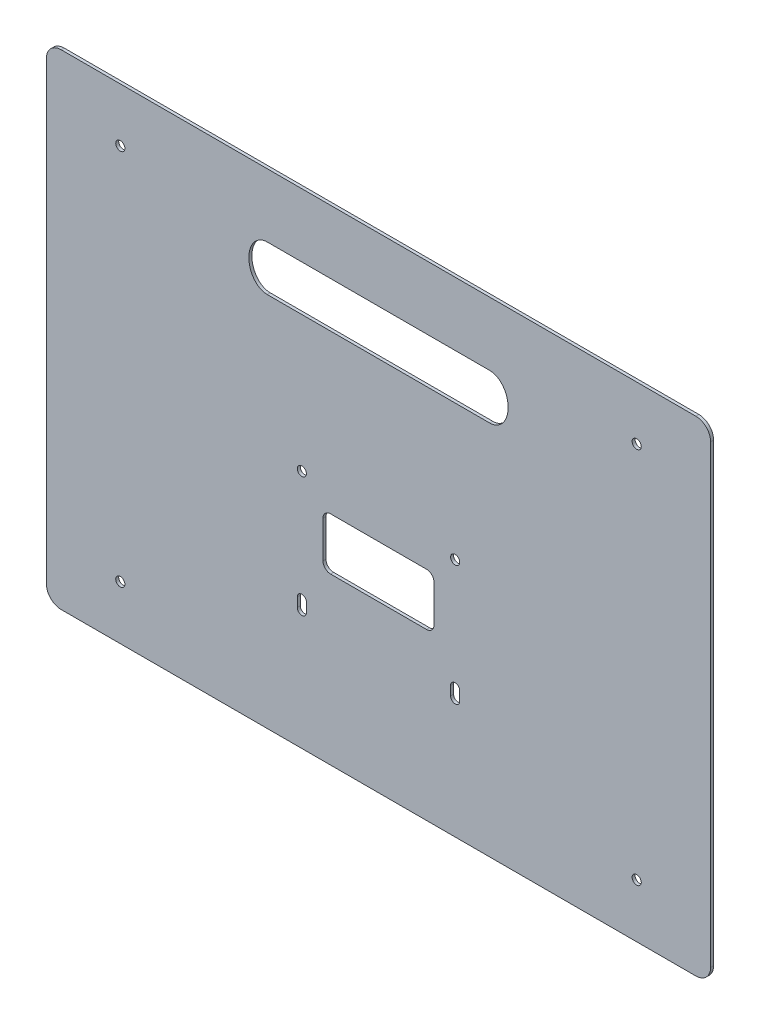
SolidWorks part; units mm, degrees
ref_plane "Front Plane" through (0, 0, 0) normal (0, 0, 1) x (1, 0, 0)
ref_plane "Top Plane" through (0, 0, 0) normal (0, 1, 0) x (1, 0, 0)
ref_plane "Right Plane" through (0, 0, 0) normal (1, 0, 0) x (0, 0, -1)
sketch "Sketch2" plane through (0, 0, 0) normal (0, 0, 1) x (1, 0, 0)
  line L1 (-225.24, 164.41) -> (225.24, 164.41)
  line L2 (-225.24, 164.41) -> (-225.24, -164.41)
  line L3 (-225.24, -164.41) -> (225.24, -164.41)
  line L4 (225.24, 164.41) -> (225.24, -164.41)
  line L5 (-225.24, 164.41) -> (225.24, -164.41) construction
  line L6 (-225.24, -164.41) -> (225.24, 164.41) construction
  point P0 (0, 0)
  dimension "Length 1" = 450.48
  dimension "Length 2" = 328.82
extrude "Boss-Extrude1" add sketch "Sketch2" along normal blind 2.032
sketch "Sketch3" plane through (0, 0, 2.032) normal (0, 0, 1) x (1, 0, 0)
  circle A0 centre (-175.117, 128.01) radius 3.1
  circle A1 centre (175.117, 128.01) radius 3.1
  circle A8 centre (-175.1171, -128.01) radius 3.1
  circle A9 centre (175.1169, -128.01) radius 3.1
  dimension "D1" = 6.2
extrude "Cut-Extrude1" cut sketch "Sketch3" against normal through all both and the other way through all
fillet "Fillet1" radius 10 4 edges at (-225.24, -164.41, 1.016) (225.24, -164.41, 1.016) (225.24, 164.41, 1.016) (-225.24, 164.41, 1.016)
sketch "Sketch4" [suppressed] plane through (0, 0, 0) normal (0, 0, -1) x (-1, 0, 0)
  circle A0 centre (-423.777, 128.01) radius 3.1
  circle A1 centre (423.777, 128.01) radius 3.1
  circle A2 centre (423.777, -128.01) radius 3.1
  circle A3 centre (-423.777, -128.01) radius 3.1
  dimension "D1" = 6.2
extrude "Cut-Extrude2" [suppressed] cut sketch "Sketch4" against normal through all both and the other way through all
fillet "Fillet2" [suppressed] radius 10
sketch "Sketch5" [suppressed] plane through (0, 0, 0) normal (0, 0, -1) x (-1, 0, 0)
  circle A0 centre (-175.117, -437.5) radius 3.1
  circle A1 centre (175.1169, -437.5) radius 3.1
  circle A2 centre (175.1169, 437.5) radius 3.1
  circle A3 centre (-175.117, 437.5) radius 3.1
  dimension "D1" = 6.2
extrude "Cut-Extrude3" [suppressed] cut sketch "Sketch5" against normal through all both and the other way through all
fillet "Fillet3" [suppressed] radius 10
sketch "Sketch6" [suppressed] plane through (0, 0, 0) normal (0, 0, -1) x (-1, 0, 0)
  circle A0 centre (175.9, -175.117) radius 3.1
  circle A1 centre (175.9, 175.117) radius 3.1
  circle A2 centre (-175.9, 175.117) radius 3.1
  circle A3 centre (-175.9, -175.117) radius 3.1
  dimension "D1" = 6.2
extrude "Cut-Extrude4" [suppressed] cut sketch "Sketch6" against normal through all both and the other way through all
sketch "Sketch7" [suppressed] plane through (0, 0, 2.032) normal (0, 0, 1) x (1, 0, 0)
  circle A0 centre (-139.6, -129.6148) radius 3.1
  circle A1 centre (-139.6, 138.5552) radius 3.1
  circle A2 centre (139.6, 151.166) radius 3.1
  circle A3 centre (139.6, -129.36) radius 3.1
  dimension "D1" = 6.2
extrude "Cut-Extrude5" [suppressed] cut sketch "Sketch7" against normal through all both and the other way through all
fillet "Fillet4" [suppressed] radius 10
sketch "Sketch8" plane through (0, 0, 2.032) normal (0, 0, 1) x (1, 0, 0)
  line L0 (-37.3761, -47.01) -> (-37.3761, -22.01) construction
  line L1 (32.5, -51.886) -> (-32.5, -51.886) construction
  line L2 (37.376, -22.01) -> (37.376, -47.01) construction
  line L3 (-32.5, -17.1339) -> (32.5, -17.1339) construction
  line L4 (-37.3761, -47.01) -> (-37.3761, -22.01) construction
  line L5 (32.5, -51.886) -> (-32.5, -51.886) construction
  line L6 (37.376, -22.01) -> (37.376, -47.01) construction
  line L7 (-32.5, -17.1339) -> (32.5, -17.1339) construction
  line L8 (-37.6761, -47.01) -> (-37.6761, -22.01)
  line L9 (32.5, -52.186) -> (-32.5, -52.186)
  line L10 (37.676, -22.01) -> (37.676, -47.01)
  line L11 (-32.5, -16.8339) -> (32.5, -16.8339)
  arc A0 (-37.3761, -47.01) -> (-32.5, -51.886) centre (-32.5, -47.01) ccw construction
  arc A1 (32.5, -51.886) -> (37.376, -47.01) centre (32.5, -47.01) ccw construction
  arc A2 (37.376, -22.01) -> (32.5, -17.1339) centre (32.5, -22.01) ccw construction
  arc A3 (-32.5, -17.1339) -> (-37.3761, -22.01) centre (-32.5, -22.01) ccw construction
  arc A4 (-37.3761, -47.01) -> (-32.5, -51.886) centre (-32.5, -47.01) ccw construction
  arc A5 (32.5, -51.886) -> (37.376, -47.01) centre (32.5, -47.01) ccw construction
  arc A6 (37.376, -22.01) -> (32.5, -17.1339) centre (32.5, -22.01) ccw construction
  arc A7 (-32.5, -17.1339) -> (-37.3761, -22.01) centre (-32.5, -22.01) ccw construction
  arc A8 (-32.5, -16.8339) -> (-37.6761, -22.01) centre (-32.5, -22.01) ccw
  arc A9 (-37.6761, -47.01) -> (-32.5, -52.186) centre (-32.5, -47.01) ccw
  arc A10 (32.5, -52.186) -> (37.676, -47.01) centre (32.5, -47.01) ccw
  arc A11 (37.676, -22.01) -> (32.5, -16.8339) centre (32.5, -22.01) ccw
  dimension "D1" = 0.3
extrude "Cut-Extrude6" cut sketch "Sketch8" against normal through all
sketch "Sketch9" plane through (0, 0, 2.032) normal (0, 0, 1) x (1, 0, 0)
  line L0 (-51.9979, -76.9078) -> (-51.9979, -83.1078) construction
  line L1 (-48.8979, -76.9078) -> (-48.8979, -83.1078)
  line L2 (-55.0979, -76.9078) -> (-55.0979, -83.1078)
  line L3 (51.9978, -76.9078) -> (51.9978, -83.1078) construction
  line L4 (55.0978, -76.9078) -> (55.0978, -83.1078)
  line L5 (48.8978, -76.9078) -> (48.8978, -83.1078)
  circle A0 centre (-51.9979, -1.5121) radius 3.1
  circle A1 centre (51.9978, -1.5121) radius 3.1
  circle A2 centre (-51.9979, -80.0078) radius 3.1 construction
  arc A3 (-48.8979, -76.9078) -> (-55.0979, -76.9078) centre (-51.9979, -76.9078) ccw
  arc A4 (-55.0979, -83.1078) -> (-48.8979, -83.1078) centre (-51.9979, -83.1078) ccw
  circle A5 centre (51.9978, -80.0078) radius 3.1 construction
  arc A6 (55.0978, -76.9078) -> (48.8978, -76.9078) centre (51.9978, -76.9078) ccw
  arc A7 (48.8978, -83.1078) -> (55.0978, -83.1078) centre (51.9978, -83.1078) ccw
  point P11 (-51.9979, -80.0078)
  point P17 (51.9978, -80.0078)
  dimension "D1" = 6.2
extrude "Cut-Extrude7" cut sketch "Sketch9" against normal through all
sketch "Sketch10" plane through (0, 0, 2.032) normal (0, 0, 1) x (1, 0, 0)
  line L0 (90, 90.8143) -> (-90, 90.8143) construction
  line L1 (75.5, 121.0648) -> (-75.5, 121.0648) construction
  line L2 (75.5, 90.8143) -> (-75.5, 90.8143) construction
  line L3 (75.5, 121.0648) -> (-75.5, 121.0648) construction
  line L4 (75.5, 90.5143) -> (-75.5, 90.5143)
  line L5 (75.5, 121.3648) -> (-75.5, 121.3648)
  spline S0 degree 3 poles (4074.4833, 130.809) (69.0697, 120.8495) (74.3193, 121.0678) (75.5298, 121.0647) (75.5326, 121.0647) (75.6464, 121.0643) (75.8632, 121.0597) (76.1642, 121.0437) (76.381, 121.0257) (76.5878, 121.0048) (76.7942, 120.9803) (77.0603, 120.9413) (77.3248, 120.8952) (77.5598, 120.8477) (77.7949, 120.7947) (77.9818, 120.7481) (78.1109, 120.7132) (78.2822, 120.6658) (78.5457, 120.5872) (78.9382, 120.4526) (79.2301, 120.3392) (79.3912, 120.2721) (79.5867, 120.1894) (79.8287, 120.0797) (80.0659, 119.9615) (80.3074, 119.8374) (80.4668, 119.7503) (80.8016, 119.5566) (81.1538, 119.3396) (81.5223, 119.0841) (81.7178, 118.9395) (81.8836, 118.8158) (82.0678, 118.6719) (82.2476, 118.5231) (82.4279, 118.3716) (82.5907, 118.2288) (82.7493, 118.0824) (82.9322, 117.9119) (83.2327, 117.6176) (83.6639, 117.1527) (83.9602, 116.8013) (84.1153, 116.6069) (84.2773, 116.4024) (84.4141, 116.2207) (84.6783, 115.8519) (84.9333, 115.4777) (85.2917, 114.8964) (85.6175, 114.311) (85.8168, 113.9147) (86.0153, 113.4997) (86.199, 113.0919) (86.3667, 112.6759) (86.5131, 112.2932) (86.6057, 112.0372) (86.6922, 111.7793) (86.7672, 111.5516) (86.8201, 111.3823) (86.9423, 110.9692) (87.0765, 110.4773) (87.247, 109.7286) (87.3625, 109.1005) (87.4598, 108.4609) (87.5282, 107.8937) (87.5661, 107.4468) (87.5939, 107.0493) (87.6148, 106.6536) (87.6234, 106.2582) (87.6251, 106.0243) (87.6252, 105.9711) (87.6249, 105.6521) (87.6131, 105.121) (87.5623, 104.3289) (87.4962, 103.7081) (87.4136, 103.0987) (87.3259, 102.565) (87.2377, 102.1278) (87.1497, 101.7237) (87.0462, 101.2874) (86.9261, 100.8539) (86.8399, 100.5642) (86.8173, 100.4902) (86.7193, 100.1763) (86.5601, 99.7025) (86.2936, 99.0104) (86.0691, 98.4959) (85.9353, 98.2118) (85.8046, 97.939) (85.5968, 97.5281) (85.2615, 96.9315) (84.9154, 96.3749) (84.674, 96.0215) (84.4707, 95.7372) (84.3836, 95.6191) (84.1969, 95.3742) (84.0085, 95.1357) (83.8127, 94.9039) (83.5714, 94.6273) (83.2684, 94.2969) (82.801, 93.8368) (82.325, 93.4136) (81.9762, 93.1336) (81.7857, 92.9898) (81.6442, 92.8839) (81.4108, 92.7157) (81.0521, 92.477) (80.7023, 92.2626) (80.4711, 92.1321) (80.188, 91.9784) (79.8408, 91.802) (79.3125, 91.5689) (78.7817, 91.3682) (78.4002, 91.2473) (78.1974, 91.1898) (78.1177, 91.1676) (77.9122, 91.1121) (77.5556, 91.0277) (77.1709, 90.9552) (76.9362, 90.9195) (76.822, 90.9037) (76.7327, 90.8917) (76.589, 90.8744) (76.4218, 90.8572) (76.2707, 90.8443) (76.119, 90.8335) (75.9751, 90.8254) (75.8173, 90.819) (75.6699, 90.8154) (75.5675, 90.8144) (75.515, 90.8143) (75.5096, 90.8143) (74.8444, 90.8139) (88.5922, 90.8832) (4071.7038, 91.2138) knots -0.003013 -0.003013 -0.003013 -0.003013 0.000024 0.000024 0.000031 0.000031 0.00032 0.000611 0.000881 0.000959 0.001235 0.001516 0.001798 0.002081 0.002271 0.00255 0.002673 0.002673 0.003081 0.003491 0.003902 0.004009 0.004009 0.004534 0.004802 0.004802 0.005346 0.005346 0.00596 0.006584 0.006682 0.006682 0.007198 0.007375 0.007375 0.007897 0.008019 0.008019 0.008644 0.009276 0.009915 0.010016 0.010016 0.010692 0.010692 0.01136 0.012037 0.01273 0.013365 0.013365 0.014106 0.014701 0.014701 0.015325 0.01551 0.01551 0.016038 0.016038 0.016796 0.017562 0.018339 0.018711 0.0195 0.020047 0.020047 0.020686 0.021225 0.021225 0.021384 0.021384 0.022179 0.022975 0.023768 0.024057 0.024824 0.025393 0.025393 0.026061 0.026729 0.026729 0.02696 0.02696 0.027709 0.028454 0.029189 0.029402 0.029402 0.030103 0.030794 0.031468 0.032075 0.032075 0.032512 0.032512 0.032989 0.033412 0.033412 0.03408 0.034748 0.035373 0.035987 0.036085 0.036085 0.036513 0.036938 0.037359 0.037729 0.037729 0.03832 0.038894 0.039463 0.040026 0.040094 0.040094 0.040274 0.04073 0.041182 0.041431 0.041431 0.041522 0.041701 0.041881 0.04206 0.042186 0.042356 0.042495 0.042636 0.042751 0.042751 0.042763 0.042763 0.044389 0.044389 0.044389 0.044389 weights 1 1 1 1 1 1 1 1 1 1 1 1 1 1 1 1 1 1 1 1 1 1 1 1 1 1 1 1 1 1 1 1 1 1 1 1 1 1 1 1 1 1 1 1 1 1 1 1 1 1 1 1 1 1 1 1 1 1 1 1 1 1 1 1 1 1 1 1 1 1 1 1 1 1 1 1 1 1 1 1 1 1 1 1 1 1 1 1 1 1 1 1 1 1 1 1 1 1 1 1 1 1 1 1 1 1 1 1 1 1 1 1 1 1 1 1 1 1 1 1 1 1 1 1 1 1 1 1 1 1 1 1 1 only from (75.5, 121.0648) to (75.5, 90.8143) construction
  spline S1 degree 3 poles (-4072.2468, 91.1237) (-66.6932, 90.8821) (-74.8103, 90.8131) (-75.5178, 90.8143) (-75.5188, 90.8143) (-75.6217, 90.8145) (-75.8102, 90.8179) (-76.0955, 90.831) (-76.3619, 90.851) (-76.5858, 90.8739) (-76.7898, 90.8988) (-76.9915, 90.9272) (-77.2231, 90.9655) (-77.4535, 91.0092) (-77.6838, 91.0585) (-77.9135, 91.1133) (-78.0691, 91.1542) (-78.2957, 91.2169) (-78.5939, 91.3066) (-79.0185, 91.4558) (-79.292, 91.5651) (-79.5791, 91.6863) (-79.8887, 91.8262) (-80.19, 91.98) (-80.431, 92.1099) (-80.5257, 92.1628) (-80.8023, 92.3227) (-81.1645, 92.5459) (-81.531, 92.801) (-81.7204, 92.9414) (-81.86, 93.0454) (-82.1004, 93.2319) (-82.4461, 93.5213) (-82.6659, 93.719) (-82.9234, 93.9587) (-83.2202, 94.2488) (-83.646, 94.7063) (-83.9884, 95.1104) (-84.1878, 95.3632) (-84.3522, 95.5769) (-84.4471, 95.7045) (-84.6398, 95.973) (-84.836, 96.257) (-85.0675, 96.6184) (-85.2256, 96.8798) (-85.2925, 96.9937) (-85.434, 97.2372) (-85.6646, 97.6556) (-85.9851, 98.3049) (-86.2393, 98.8843) (-86.3829, 99.2453) (-86.4494, 99.4187) (-86.55, 99.6841) (-86.6603, 99.9986) (-86.7491, 100.2733) (-86.796, 100.4205) (-86.8377, 100.5557) (-86.8778, 100.6914) (-86.9586, 100.968) (-87.0905, 101.4582) (-87.2577, 102.2029) (-87.3631, 102.7847) (-87.4242, 103.1837) (-87.4447, 103.3291) (-87.4978, 103.7198) (-87.5689, 104.3709) (-87.6172, 105.2208) (-87.6253, 105.7445) (-87.6253, 105.9682) (-87.6252, 105.997) (-87.6239, 106.2925) (-87.6102, 106.8253) (-87.5586, 107.5863) (-87.4824, 108.2948) (-87.3824, 108.9904) (-87.2522, 109.7032) (-87.0975, 110.3876) (-86.9658, 110.8838) (-86.8849, 111.1642) (-86.8565, 111.2593) (-86.8202, 111.38) (-86.7924, 111.4698) (-86.7084, 111.7335) (-86.617, 112.0056) (-86.5018, 112.3221) (-86.4473, 112.4659) (-86.3387, 112.7484) (-86.1745, 113.1489) (-85.9253, 113.6947) (-85.6673, 114.2147) (-85.3669, 114.7671) (-85.0165, 115.3478) (-84.7388, 115.7647) (-84.5819, 115.9866) (-84.4547, 116.1642) (-84.3562, 116.297) (-84.1525, 116.5617) (-83.9899, 116.7652) (-83.8222, 116.9634) (-83.7278, 117.0727) (-83.6931, 117.1124) (-83.512, 117.3171) (-83.2145, 117.6374) (-82.7539, 118.0859) (-82.3108, 118.4763) (-81.9806, 118.7415) (-81.7867, 118.8888) (-81.7261, 118.9339) (-81.5923, 119.0328) (-81.36, 119.1984) (-81.006, 119.4314) (-80.7579, 119.5818) (-80.6329, 119.6543) (-80.5302, 119.7137) (-80.4331, 119.768) (-80.1632, 119.9135) (-79.8189, 120.0873) (-79.2869, 120.3208) (-78.7504, 120.5219) (-78.374, 120.6396) (-78.1216, 120.7105) (-77.9102, 120.7674) (-77.5659, 120.8488) (-77.1858, 120.9214) (-76.9471, 120.958) (-76.8184, 120.9759) (-76.7272, 120.988) (-76.582, 121.0054) (-76.4149, 121.0225) (-76.2649, 121.0352) (-76.1143, 121.0458) (-75.972, 121.0538) (-75.8151, 121.0601) (-75.6689, 121.0637) (-75.5671, 121.0646) (-75.515, 121.0648) (-75.5096, 121.0648) (-74.8476, 121.0651) (-88.6415, 120.9964) (-4071.2969, 120.6689) knots -0.001623 -0.001623 -0.001623 -0.001623 0.000013 0.000013 0.000016 0.000016 0.000262 0.000488 0.000778 0.001021 0.001162 0.001413 0.001666 0.001921 0.002175 0.002427 0.002667 0.002667 0.00313 0.003594 0.004001 0.004001 0.004517 0.00501 0.00501 0.005334 0.005334 0.005966 0.006608 0.006668 0.006668 0.007126 0.007571 0.008002 0.008002 0.008616 0.009237 0.009867 0.010196 0.010196 0.010669 0.010669 0.011178 0.011692 0.011939 0.012084 0.012084 0.012777 0.013509 0.014247 0.014667 0.014667 0.0148 0.015513 0.015656 0.015656 0.015971 0.016076 0.016076 0.016826 0.017586 0.018355 0.018595 0.018795 0.018795 0.019775 0.020751 0.02133 0.02133 0.021415 0.021415 0.022207 0.023001 0.023696 0.024344 0.025112 0.025872 0.026446 0.026646 0.026742 0.026742 0.027021 0.027021 0.027563 0.027871 0.02802 0.02802 0.028771 0.029311 0.029815 0.03051 0.031195 0.031844 0.032003 0.032003 0.032493 0.032493 0.032991 0.033263 0.033263 0.033421 0.033421 0.034077 0.034725 0.035343 0.035843 0.035988 0.036067 0.036067 0.036482 0.036912 0.037319 0.037341 0.037341 0.037673 0.037673 0.038257 0.038828 0.039418 0.039978 0.040009 0.040201 0.04063 0.041056 0.041342 0.041342 0.04144 0.041618 0.041798 0.041977 0.042099 0.042269 0.042405 0.042545 0.04266 0.04266 0.042671 0.042671 0.04429 0.04429 0.04429 0.04429 weights 1 1 1 1 1 1 1 1 1 1 1 1 1 1 1 1 1 1 1 1 1 1 1 1 1 1 1 1 1 1 1 1 1 1 1 1 1 1 1 1 1 1 1 1 1 1 1 1 1 1 1 1 1 1 1 1 1 1 1 1 1 1 1 1 1 1 1 1 1 1 1 1 1 1 1 1 1 1 1 1 1 1 1 1 1 1 1 1 1 1 1 1 1 1 1 1 1 1 1 1 1 1 1 1 1 1 1 1 1 1 1 1 1 1 1 1 1 1 1 1 1 1 1 1 1 1 1 1 1 1 1 1 1 1 1 1 1 1 1 1 only from (-75.5, 90.8143) to (-75.5, 121.0648) construction
  spline S2 degree 3 poles (75.5, 121.0648) (75.5079, 121.0648) (75.5205, 121.0647) (75.5326, 121.0647) (75.6464, 121.0643) (75.8632, 121.0597) (76.1642, 121.0437) (76.381, 121.0257) (76.5878, 121.0048) (76.7942, 120.9803) (77.0603, 120.9413) (77.3248, 120.8952) (77.5598, 120.8477) (77.7949, 120.7947) (77.9818, 120.7481) (78.1109, 120.7132) (78.2822, 120.6658) (78.5457, 120.5872) (78.9382, 120.4526) (79.2301, 120.3392) (79.3912, 120.2721) (79.5867, 120.1894) (79.8287, 120.0797) (80.0659, 119.9615) (80.3074, 119.8374) (80.4668, 119.7503) (80.8016, 119.5566) (81.1538, 119.3396) (81.5223, 119.0841) (81.7178, 118.9395) (81.8836, 118.8158) (82.0678, 118.6719) (82.2476, 118.5231) (82.4279, 118.3716) (82.5907, 118.2288) (82.7493, 118.0824) (82.9322, 117.9119) (83.2327, 117.6176) (83.6639, 117.1527) (83.9602, 116.8013) (84.1153, 116.6069) (84.2773, 116.4024) (84.4141, 116.2207) (84.6783, 115.8519) (84.9333, 115.4777) (85.2917, 114.8964) (85.6175, 114.311) (85.8168, 113.9147) (86.0153, 113.4997) (86.199, 113.0919) (86.3667, 112.6759) (86.5131, 112.2932) (86.6057, 112.0372) (86.6922, 111.7793) (86.7672, 111.5516) (86.8201, 111.3823) (86.9423, 110.9692) (87.0765, 110.4773) (87.247, 109.7286) (87.3625, 109.1005) (87.4598, 108.4609) (87.5282, 107.8937) (87.5661, 107.4468) (87.5939, 107.0493) (87.6148, 106.6536) (87.6234, 106.2582) (87.6251, 106.0243) (87.6252, 105.9711) (87.6249, 105.6521) (87.6131, 105.121) (87.5623, 104.3289) (87.4962, 103.7081) (87.4136, 103.0987) (87.3259, 102.565) (87.2377, 102.1278) (87.1497, 101.7237) (87.0462, 101.2874) (86.9261, 100.8539) (86.8399, 100.5642) (86.8173, 100.4902) (86.7193, 100.1763) (86.5601, 99.7025) (86.2936, 99.0104) (86.0691, 98.4959) (85.9353, 98.2118) (85.8046, 97.939) (85.5968, 97.5281) (85.2615, 96.9315) (84.9154, 96.3749) (84.674, 96.0215) (84.4707, 95.7372) (84.3836, 95.6191) (84.1969, 95.3742) (84.0085, 95.1357) (83.8127, 94.9039) (83.5714, 94.6273) (83.2684, 94.2969) (82.801, 93.8368) (82.325, 93.4136) (81.9762, 93.1336) (81.7857, 92.9898) (81.6442, 92.8839) (81.4108, 92.7157) (81.0521, 92.477) (80.7023, 92.2626) (80.4711, 92.1321) (80.188, 91.9784) (79.8408, 91.802) (79.3125, 91.5689) (78.7817, 91.3682) (78.4002, 91.2473) (78.1974, 91.1898) (78.1177, 91.1676) (77.9122, 91.1121) (77.5556, 91.0277) (77.1709, 90.9552) (76.9362, 90.9195) (76.822, 90.9037) (76.7327, 90.8917) (76.589, 90.8744) (76.4218, 90.8572) (76.2707, 90.8443) (76.119, 90.8335) (75.9751, 90.8254) (75.8173, 90.819) (75.6699, 90.8154) (75.5675, 90.8144) (75.515, 90.8143) (75.5076, 90.8143) (75.5015, 90.8143) (75.5, 90.8143) knots 0 0 0 0 0.000024 0.000031 0.000031 0.00032 0.000611 0.000881 0.000959 0.001235 0.001516 0.001798 0.002081 0.002271 0.00255 0.002673 0.002673 0.003081 0.003491 0.003902 0.004009 0.004009 0.004534 0.004802 0.004802 0.005346 0.005346 0.00596 0.006584 0.006682 0.006682 0.007198 0.007375 0.007375 0.007897 0.008019 0.008019 0.008644 0.009276 0.009915 0.010016 0.010016 0.010692 0.010692 0.01136 0.012037 0.01273 0.013365 0.013365 0.014106 0.014701 0.014701 0.015325 0.01551 0.01551 0.016038 0.016038 0.016796 0.017562 0.018339 0.018711 0.0195 0.020047 0.020047 0.020686 0.021225 0.021225 0.021384 0.021384 0.022179 0.022975 0.023768 0.024057 0.024824 0.025393 0.025393 0.026061 0.026729 0.026729 0.02696 0.02696 0.027709 0.028454 0.029189 0.029402 0.029402 0.030103 0.030794 0.031468 0.032075 0.032075 0.032512 0.032512 0.032989 0.033412 0.033412 0.03408 0.034748 0.035373 0.035987 0.036085 0.036085 0.036513 0.036938 0.037359 0.037729 0.037729 0.03832 0.038894 0.039463 0.040026 0.040094 0.040094 0.040274 0.04073 0.041182 0.041431 0.041431 0.041522 0.041701 0.041881 0.04206 0.042186 0.042356 0.042495 0.042636 0.042751 0.042751 0.042763 0.042767 0.042767 0.042767 0.042767 weights 1 1 1 1 1 1 1 1 1 1 1 1 1 1 1 1 1 1 1 1 1 1 1 1 1 1 1 1 1 1 1 1 1 1 1 1 1 1 1 1 1 1 1 1 1 1 1 1 1 1 1 1 1 1 1 1 1 1 1 1 1 1 1 1 1 1 1 1 1 1 1 1 1 1 1 1 1 1 1 1 1 1 1 1 1 1 1 1 1 1 1 1 1 1 1 1 1 1 1 1 1 1 1 1 1 1 1 1 1 1 1 1 1 1 1 1 1 1 1 1 1 1 1 1 1 1 1 1 1 1 1 construction
  spline S3 degree 3 poles (-75.5, 90.8143) (-75.5046, 90.8143) (-75.512, 90.8143) (-75.5188, 90.8143) (-75.6217, 90.8145) (-75.8102, 90.8179) (-76.0955, 90.831) (-76.3619, 90.851) (-76.5858, 90.8739) (-76.7898, 90.8988) (-76.9915, 90.9272) (-77.2231, 90.9655) (-77.4535, 91.0092) (-77.6838, 91.0585) (-77.9135, 91.1133) (-78.0691, 91.1542) (-78.2957, 91.2169) (-78.5939, 91.3066) (-79.0185, 91.4558) (-79.292, 91.5651) (-79.5791, 91.6863) (-79.8887, 91.8262) (-80.19, 91.98) (-80.431, 92.1099) (-80.5257, 92.1628) (-80.8023, 92.3227) (-81.1645, 92.5459) (-81.531, 92.801) (-81.7204, 92.9414) (-81.86, 93.0454) (-82.1004, 93.2319) (-82.4461, 93.5213) (-82.6659, 93.719) (-82.9234, 93.9587) (-83.2202, 94.2488) (-83.646, 94.7063) (-83.9884, 95.1104) (-84.1878, 95.3632) (-84.3522, 95.5769) (-84.4471, 95.7045) (-84.6398, 95.973) (-84.836, 96.257) (-85.0675, 96.6184) (-85.2256, 96.8798) (-85.2925, 96.9937) (-85.434, 97.2372) (-85.6646, 97.6556) (-85.9851, 98.3049) (-86.2393, 98.8843) (-86.3829, 99.2453) (-86.4494, 99.4187) (-86.55, 99.6841) (-86.6603, 99.9986) (-86.7491, 100.2733) (-86.796, 100.4205) (-86.8377, 100.5557) (-86.8778, 100.6914) (-86.9586, 100.968) (-87.0905, 101.4582) (-87.2577, 102.2029) (-87.3631, 102.7847) (-87.4242, 103.1837) (-87.4447, 103.3291) (-87.4978, 103.7198) (-87.5689, 104.3709) (-87.6172, 105.2208) (-87.6253, 105.7445) (-87.6253, 105.9682) (-87.6252, 105.997) (-87.6239, 106.2925) (-87.6102, 106.8253) (-87.5586, 107.5863) (-87.4824, 108.2948) (-87.3824, 108.9904) (-87.2522, 109.7032) (-87.0975, 110.3876) (-86.9658, 110.8838) (-86.8849, 111.1642) (-86.8565, 111.2593) (-86.8202, 111.38) (-86.7924, 111.4698) (-86.7084, 111.7335) (-86.617, 112.0056) (-86.5018, 112.3221) (-86.4473, 112.4659) (-86.3387, 112.7484) (-86.1745, 113.1489) (-85.9253, 113.6947) (-85.6673, 114.2147) (-85.3669, 114.7671) (-85.0165, 115.3478) (-84.7388, 115.7647) (-84.5819, 115.9866) (-84.4547, 116.1642) (-84.3562, 116.297) (-84.1525, 116.5617) (-83.9899, 116.7652) (-83.8222, 116.9634) (-83.7278, 117.0727) (-83.6931, 117.1124) (-83.512, 117.3171) (-83.2145, 117.6374) (-82.7539, 118.0859) (-82.3108, 118.4763) (-81.9806, 118.7415) (-81.7867, 118.8888) (-81.7261, 118.9339) (-81.5923, 119.0328) (-81.36, 119.1984) (-81.006, 119.4314) (-80.7579, 119.5818) (-80.6329, 119.6543) (-80.5302, 119.7137) (-80.4331, 119.768) (-80.1632, 119.9135) (-79.8189, 120.0873) (-79.2869, 120.3208) (-78.7504, 120.5219) (-78.374, 120.6396) (-78.1216, 120.7105) (-77.9102, 120.7674) (-77.5659, 120.8488) (-77.1858, 120.9214) (-76.9471, 120.958) (-76.8184, 120.9759) (-76.7272, 120.988) (-76.582, 121.0054) (-76.4149, 121.0225) (-76.2649, 121.0352) (-76.1143, 121.0458) (-75.972, 121.0538) (-75.8151, 121.0601) (-75.6689, 121.0637) (-75.5671, 121.0646) (-75.515, 121.0648) (-75.5076, 121.0648) (-75.5015, 121.0648) (-75.5, 121.0648) knots 0 0 0 0 0.000013 0.000016 0.000016 0.000262 0.000488 0.000778 0.001021 0.001162 0.001413 0.001666 0.001921 0.002175 0.002427 0.002667 0.002667 0.00313 0.003594 0.004001 0.004001 0.004517 0.00501 0.00501 0.005334 0.005334 0.005966 0.006608 0.006668 0.006668 0.007126 0.007571 0.008002 0.008002 0.008616 0.009237 0.009867 0.010196 0.010196 0.010669 0.010669 0.011178 0.011692 0.011939 0.012084 0.012084 0.012777 0.013509 0.014247 0.014667 0.014667 0.0148 0.015513 0.015656 0.015656 0.015971 0.016076 0.016076 0.016826 0.017586 0.018355 0.018595 0.018795 0.018795 0.019775 0.020751 0.02133 0.02133 0.021415 0.021415 0.022207 0.023001 0.023696 0.024344 0.025112 0.025872 0.026446 0.026646 0.026742 0.026742 0.027021 0.027021 0.027563 0.027871 0.02802 0.02802 0.028771 0.029311 0.029815 0.03051 0.031195 0.031844 0.032003 0.032003 0.032493 0.032493 0.032991 0.033263 0.033263 0.033421 0.033421 0.034077 0.034725 0.035343 0.035843 0.035988 0.036067 0.036067 0.036482 0.036912 0.037319 0.037341 0.037341 0.037673 0.037673 0.038257 0.038828 0.039418 0.039978 0.040009 0.040201 0.04063 0.041056 0.041342 0.041342 0.04144 0.041618 0.041798 0.041977 0.042099 0.042269 0.042405 0.042545 0.04266 0.04266 0.042671 0.042676 0.042676 0.042676 0.042676 weights 1 1 1 1 1 1 1 1 1 1 1 1 1 1 1 1 1 1 1 1 1 1 1 1 1 1 1 1 1 1 1 1 1 1 1 1 1 1 1 1 1 1 1 1 1 1 1 1 1 1 1 1 1 1 1 1 1 1 1 1 1 1 1 1 1 1 1 1 1 1 1 1 1 1 1 1 1 1 1 1 1 1 1 1 1 1 1 1 1 1 1 1 1 1 1 1 1 1 1 1 1 1 1 1 1 1 1 1 1 1 1 1 1 1 1 1 1 1 1 1 1 1 1 1 1 1 1 1 1 1 1 1 1 1 1 1 1 1 construction
  spline S4 degree 1 poles (-75.5, 90.5143) (-75.5, 121.3648) knots 0 0 1 1 construction
  spline S5 degree 1 poles (75.5, 121.3648) (75.5, 90.5143) knots 0 0 1 1 construction
  spline S6 degree 3 poles (-75.5, 90.5143) (-75.6364, 90.5143) (-75.9178, 90.5203) (-76.4106, 90.5505) (-76.9682, 90.6146) (-77.583, 90.724) (-78.4367, 90.929) (-79.5539, 91.3171) (-81.1922, 92.1383) (-83.046, 93.5297) (-85.4559, 96.3039) (-87.4217, 100.5003) (-88.1781, 105.9528) (-87.4175, 111.3767) (-85.4702, 115.556) (-83.3502, 117.9986) (-81.9517, 119.1724) (-80.7872, 119.944) (-79.56, 120.5575) (-78.4813, 120.9369) (-77.5849, 121.1564) (-77.0009, 121.2574) (-76.5584, 121.3109) (-76.2401, 121.3392) (-75.9079, 121.3589) (-75.6314, 121.3648) (-75.5, 121.3648) knots 0 0 0 0 0.000333 0.000667 0.001334 0.002 0.002667 0.004001 0.005334 0.008002 0.010669 0.016003 0.021338 0.026672 0.032007 0.034674 0.036008 0.037341 0.038675 0.040009 0.040675 0.041342 0.041676 0.042009 0.042342 0.042676 0.042676 0.042676 0.042676
  spline S7 degree 3 poles (75.5, 121.3648) (75.7505, 121.3647) (76.2699, 121.3441) (76.935, 121.2693) (77.5771, 121.1569) (78.4459, 120.9475) (79.5593, 120.5593) (81.1959, 119.7385) (83.0542, 118.3419) (85.4627, 115.5649) (87.0341, 112.198) (87.7984, 108.6558) (87.9891, 105.9096) (87.7964, 103.2116) (87.0182, 99.6349) (85.4812, 96.3435) (83.3563, 93.8861) (81.9584, 92.712) (80.7938, 91.9388) (79.5626, 91.3225) (78.483, 90.9427) (77.5871, 90.7231) (77.0029, 90.622) (76.5596, 90.5682) (76.2408, 90.5399) (75.9082, 90.5202) (75.6315, 90.5143) (75.5, 90.5143) knots 0 0 0 0 0.000668 0.001336 0.002005 0.002673 0.004009 0.005346 0.008019 0.010692 0.016038 0.018711 0.021384 0.024056 0.026729 0.032075 0.034748 0.036085 0.037421 0.038758 0.040094 0.040762 0.041431 0.041765 0.042099 0.042433 0.042767 0.042767 0.042767 0.042767
  dimension "D1" = 0.3
extrude "Cut-Extrude8" cut sketch "Sketch10" against normal through all
